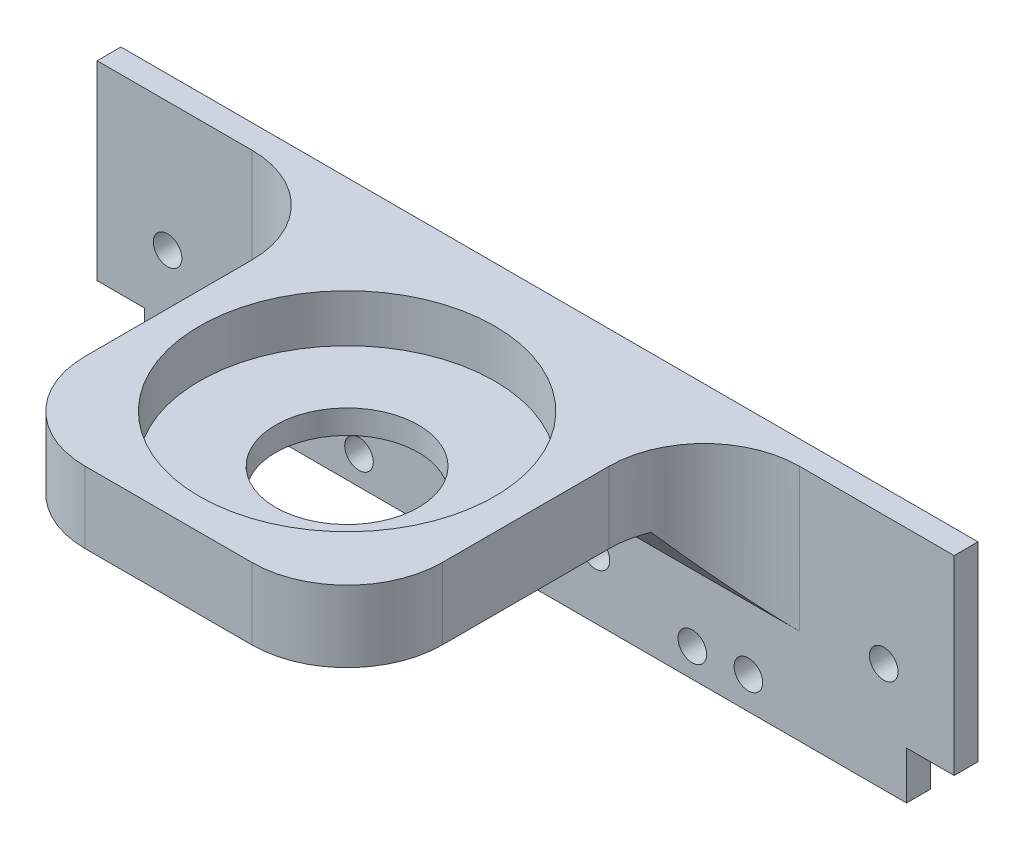
SolidWorks part; units mm, degrees
ref_plane "Plan de face" through (0, 0, 0) normal (0, 0, 1) x (1, 0, 0)
ref_plane "Plan de dessus" through (0, 0, 0) normal (0, 1, 0) x (1, 0, 0)
ref_plane "Plan de droite" through (0, 0, 0) normal (1, 0, 0) x (0, 0, -1)
sketch "Esquisse1" plane through (0, 0, 0) normal (0, 0, 1) x (1, 0, 0)
  line L0 (-84.204, 50) -> (95.796, 0) construction
  line L1 (-84.204, 0) -> (95.796, 0)
  line L2 (-84.204, 0) -> (-84.204, 50)
  line L3 (-84.204, 50) -> (95.796, 50)
  line L4 (95.796, 0) -> (95.796, 50)
  line L5 (95.796, 25) -> (5.796, 25) construction
  line L6 (5.796, 25) -> (5.796, 0) construction
  circle A0 centre (40.796, 6) radius 3 construction
  circle A1 centre (-69.406, 22.9394) radius 3 construction
  circle A2 centre (-40.9815, 6.7762) radius 3 construction
  circle A3 centre (-8.8615, 12.9011) radius 3 construction
  circle A4 centre (40.796, 6) radius 3
  circle A5 centre (-69.406, 22.9394) radius 3
  circle A6 centre (-40.9815, 6.7762) radius 3
  circle A7 centre (-8.8615, 12.9011) radius 3
  circle A8 centre (-29.204, 6) radius 3
  circle A9 centre (80.998, 22.9394) radius 3
  circle A10 centre (52.5735, 6.7762) radius 3
  circle A11 centre (20.4536, 12.9011) radius 3
extrude "Boss.-Extru.1" add sketch "Esquisse1" along normal blind 5
sketch "Esquisse2" plane through (0, 0, 5) normal (0, 0, 1) x (1, 0, 0)
  line L0 (5.796, 0) -> (5.796, 67.3568) construction
  line L1 (95.796, 50) -> (-84.204, 50) construction
  line L2 (-31.704, 35) -> (43.296, 35)
  line L3 (-31.704, 35) -> (-31.704, 50)
  line L4 (-31.704, 50) -> (43.296, 50)
  line L5 (43.296, 35) -> (43.296, 50)
  line L6 (-31.704, 35) -> (43.296, 50) construction
  line L7 (-31.704, 50) -> (43.296, 35) construction
  line L10 (-84.204, 50) -> (95.796, 0) construction
  line L11 (95.796, 0) -> (5.796, 0) construction
  line L12 (-84.204, 0) -> (95.796, 0) construction
  line L13 (5.796, 0) -> (5.796, 25) construction
  point P3 (5.796, 42.5)
  dimension "D1" = 75
  dimension "D2" = 15
extrude "Boss.-Extru.2" add sketch "Esquisse2" along normal blind 75
sketch "Esquisse3" plane through (0, 50, 0) normal (0, 1, 0) x (1, 0, 0)
  line L0 (-31.704, -80) -> (43.296, -5) construction
  line L1 (43.296, -5) -> (5.796, -5) construction
  line L2 (5.796, -5) -> (5.796, -42.5) construction
  circle A0 centre (5.796, -42.5) radius 15
  dimension "D1" = 30
extrude "Enlèv. mat.-Extru.1" cut sketch "Esquisse3" against normal up to surface (15 mm away) up to face at (5.796, 35, 42.5)
sketch "Esquisse4" plane through (0, 50, 0) normal (0, 1, 0) x (1, 0, 0)
  circle A0 centre (5.796, -42.5) radius 31
  dimension "D1" = 62
extrude "Enlèv. mat.-Extru.2" cut sketch "Esquisse4" against normal blind 10
fillet "Congé1" radius 20 2 edges at (-31.704, 42.5, 80) (43.296, 42.5, 80)
chamfer "Chanfrein1" distance 15 angle 40 1 edges at (5.796, 35, 5) first distance on face at (17.4536, 12.9011, 5)
fillet "Congé2" radius 20 2 edges at (-31.704, 35, 5) (43.296, 35, 5)
sketch "Esquisse5" plane through (0, 0, 5) normal (0, 0, 1) x (1, 0, 0)
  line L0 (95.796, 50) -> (-84.204, 0) construction
  line L1 (-84.204, 0) -> (-74.204, 0)
  line L2 (-84.204, 0) -> (-84.204, 10)
  line L3 (-84.204, 10) -> (-74.204, 10)
  line L4 (-74.204, 0) -> (-74.204, 10)
  line L5 (-84.204, 25) -> (5.796, 25) construction
  line L6 (-84.204, 50) -> (-84.204, 0) construction
  line L7 (5.796, 25) -> (5.796, 0) construction
  line L8 (-84.204, 0) -> (95.796, 0) construction
  line L9 (85.796, 0) -> (85.796, 10)
  line L10 (95.796, 0) -> (95.796, 10)
  line L11 (95.796, 0) -> (85.796, 0)
  line L12 (95.796, 10) -> (85.796, 10)
  dimension "D1" = 10
  dimension "D2" = 10
extrude "Enlèv. mat.-Extru.3" cut sketch "Esquisse5" against normal up to surface (5 mm away) up to face at (49.5735, 6.7762, 0)
